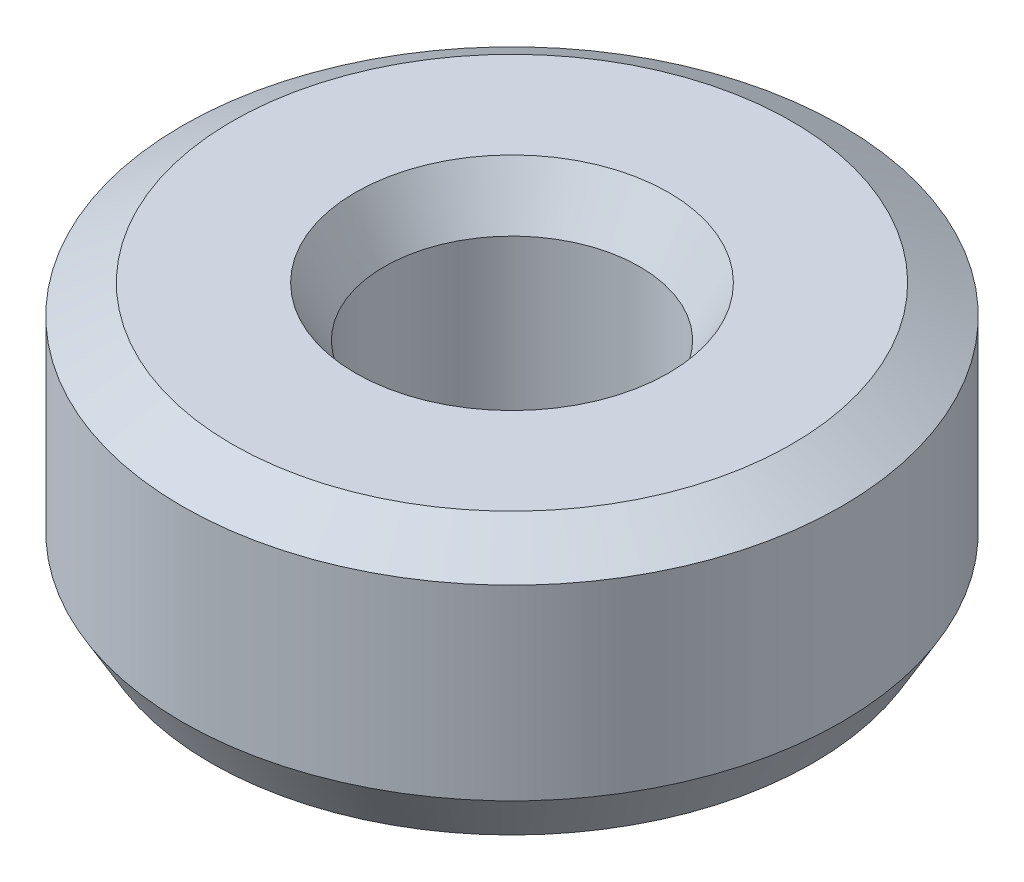
SolidWorks part; units mm, degrees
ref_plane "Front Plane" through (0, 0, 0) normal (0, 0, 1) x (1, 0, 0)
ref_plane "Top Plane" through (0, 0, 0) normal (0, 1, 0) x (1, 0, 0)
ref_plane "Right Plane" through (0, 0, 0) normal (1, 0, 0) x (0, 0, -1)
sketch "Sketch1" plane through (0, 0, 0) normal (0, 1, 0) x (1, 0, 0)
  circle A0 centre (0, 0) radius 12.5
  dimension "SLEEVE_OD" = 25
extrude "Boss-Extrude1" add sketch "Sketch1" along normal blind 10.0671
sketch "Sketch2" plane through (0, 0, 0) normal (0, 1, 0) x (1, 0, 0)
  circle A0 centre (0, 0) radius 4.8434
  dimension "BORE_D" = 9.6867
extrude "Cut-Extrude1" cut sketch "Sketch2" along normal through all
chamfer "Chamfer1" distance 1.0925 angle 60 4 edges at (0, 10.0671, 4.8434) (0, 0, 4.8434) (0, 0, 12.5) (0, 10.0671, 12.5) first distance on face at (0, 10.0671, 4.8434) first distance on face at (0, 0, 4.8434) first distance on face at (0, 10.0671, 12.5)
